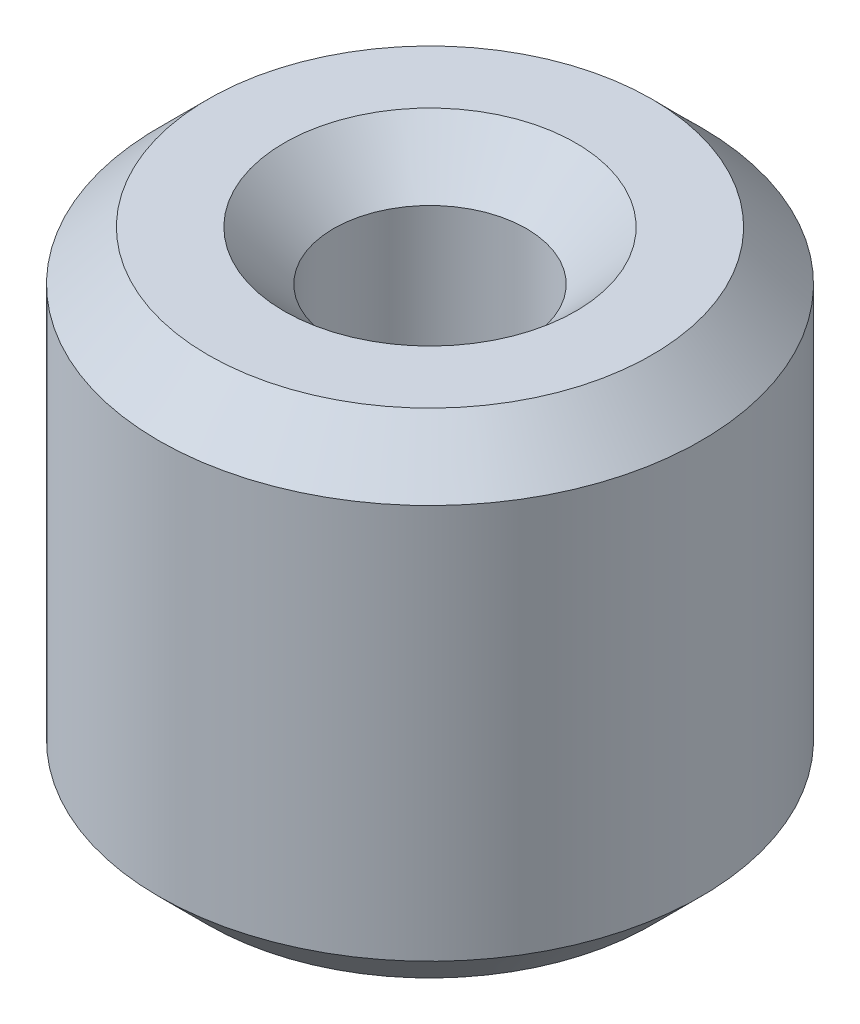
SolidWorks part; units mm, degrees
ref_plane "Front Plane" through (0, 0, 0) normal (0, 0, 1) x (1, 0, 0)
ref_plane "Top Plane" through (0, 0, 0) normal (0, 1, 0) x (1, 0, 0)
ref_plane "Right Plane" through (0, 0, 0) normal (1, 0, 0) x (0, 0, -1)
sketch "Sketch1" plane through (0, 0, 0) normal (0, 1, 0) x (1, 0, 0)
  circle A0 centre (0, 0) radius 15
  dimension "SLEEVE_OD" = 30
extrude "Boss-Extrude1" add sketch "Sketch1" along normal blind 27.2971
sketch "Sketch2" plane through (0, 0, 0) normal (0, 1, 0) x (1, 0, 0)
  circle A0 centre (0, 0) radius 5.3293
  dimension "BORE_D" = 10.6587
extrude "Cut-Extrude1" cut sketch "Sketch2" along normal through all
chamfer "Chamfer1" distance 2.734 angle 45 4 edges at (0, 27.2971, 5.3293) (0, 0, 5.3293) (0, 0, 15) (0, 27.2971, 15)
